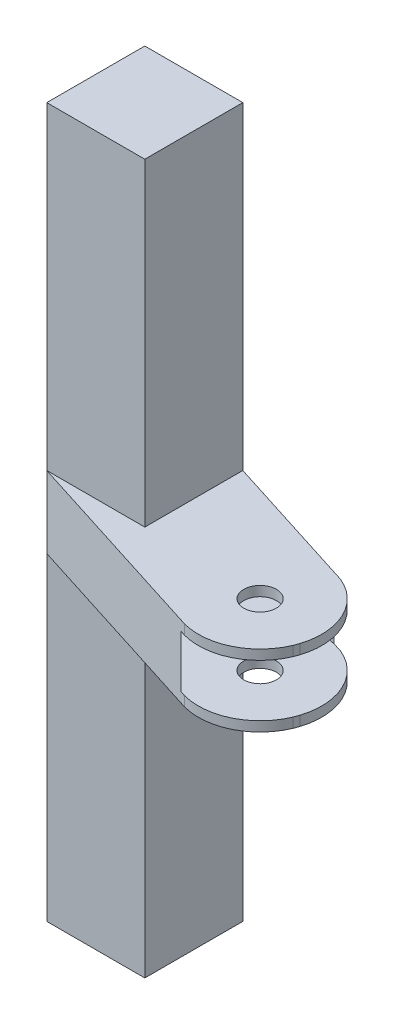
SolidWorks part; units mm, degrees
ref_plane "Front Plane" through (0, 0, 0) normal (0, 0, 1) x (1, 0, 0)
ref_plane "Top Plane" through (0, 0, 0) normal (0, 1, 0) x (1, 0, 0)
ref_plane "Right Plane" through (0, 0, 0) normal (1, 0, 0) x (0, 0, -1)
sketch "Sketch1" plane through (0, 0, 0) normal (0, 1, 0) x (1, 0, 0)
  line L1 (-36.055, 5.2706) -> (-6.055, 5.2706)
  line L2 (-36.055, 5.2706) -> (-36.055, -24.7294)
  line L3 (-36.055, -24.7294) -> (-6.055, -24.7294)
  line L4 (-6.055, 5.2706) -> (-6.055, -24.7294)
  dimension "D1" = 30
  dimension "D2" = 30
extrude "Boss-Extrude1" add sketch "Sketch1" along normal blind 217
sketch "Sketch2" plane through (0, 0, 0) normal (0, -1, 0) x (1, 0, 0)
  line L0 (-36.055, 24.7294) -> (42.0251, 49.4804)
  line L1 (42.0251, 49.4804) -> (55.0818, 14.1095)
  line L2 (55.0818, 14.1095) -> (-6.055, -5.2706)
  line L3 (-27.7535, 24.7294) -> (16.6425, 38.8027)
  line L4 (-36.055, 24.7294) -> (-6.055, 24.7294) construction
  line L5 (16.6425, 38.8027) -> (27.8002, 7.4118)
  line L7 (27.8002, 7.4118) -> (-6.055, -2.9222)
  line L8 (-6.055, 24.7294) -> (-6.055, -5.2706) construction
  circle A1 centre (30.5715, 26.0752) radius 18.8681
  circle A2 centre (30.5715, 26.0752) radius 5
  line M6 (-6.055, -5.2706) -> (-6.055, 24.7294)
  line M7 (-6.055, 24.7294) -> (-36.055, 24.7294)
  dimension "D2" = 18.85
  dimension "D1" = 37.7039
  dimension "D3" = 18.85
extrude "Boss-Extrude3" add sketch "Sketch2" against normal blind 119.5 contours A1 L0 L3 M7 | A1 L3 L7 M7 M6 | A1 L7 L2 M6 | L5 A1 | L2 A1 L1 L0 L5 A2 region at (-6.4074, 0, 32.8741) region at (25.0266, 0, 43.5675) region at (3.3975, 0, 17.3235) region at (18.3486, 0, 21.7307) region at (11.6748, 0, 1.3945)
extrude "Cut-Extrude1" cut sketch "Sketch2<5>" against normal blind 116.5 contours A1 L3 L7 M7 M6 | L5 A1 | L2 A1 L1 L0 L5 A2 region at (25.0266, 0, 43.5675) region at (3.3975, 0, 17.3235) region at (18.3486, 0, 21.7307)
sketch "Sketch2<5>" plane through (0, 0, 0) normal (0, -1, 0) x (1, 0, 0) same geometry as "Sketch2"
extrude "Boss-Extrude4" add sketch "Sketch2<6>" against normal blind 100.5 contours A1 L3 L7 M7 M6 | L5 A1 | L2 A1 L1 L0 L5 A2 region at (25.0266, 0, 43.5675) region at (3.3975, 0, 17.3235) region at (18.3486, 0, 21.7307)
sketch "Sketch2<6>" plane through (0, 0, 0) normal (0, -1, 0) x (1, 0, 0) same geometry as "Sketch2"
extrude "Cut-Extrude2" cut sketch "Sketch2<7>" against normal blind 97.5 contours L2 A1 L1 L0 L5 A2 | L5 A1 | A1 L3 L7 M7 M6 | A1 L0 L3 M7 | A1 L7 L2 M6 region at (-6.4074, 0, 32.8741) region at (25.0266, 0, 43.5675) region at (3.3975, 0, 17.3235) region at (18.3486, 0, 21.7307) region at (11.6748, 0, 1.3945)
sketch "Sketch2<7>" plane through (0, 0, 0) normal (0, -1, 0) x (1, 0, 0) same geometry as "Sketch2"
